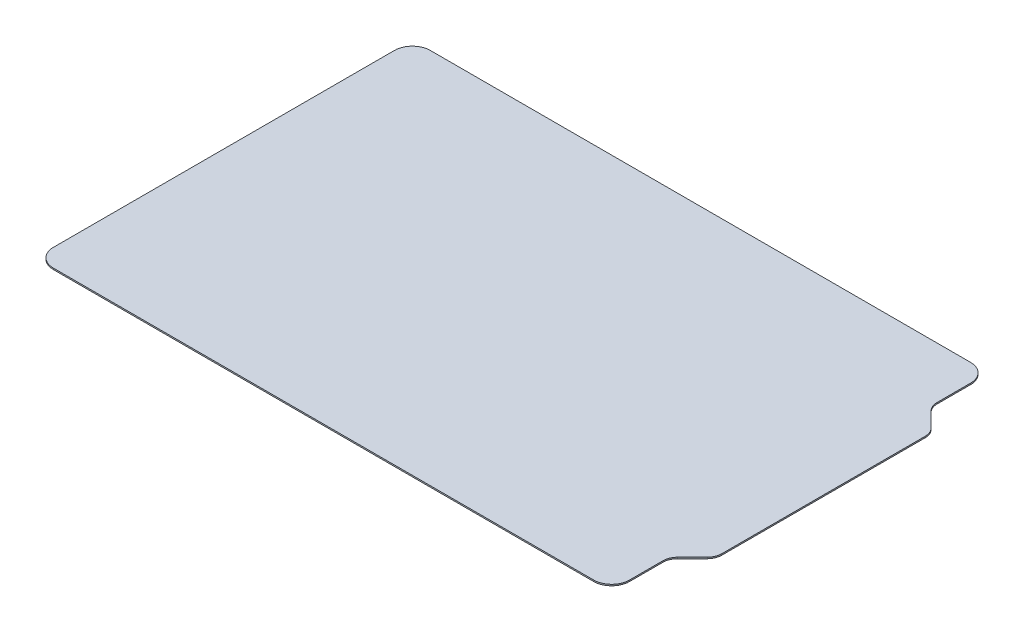
SolidWorks part; units mm, degrees
material "AISI 1020 Steel, Cold Rolled"
ref_plane "Front Plane" through (0, 0, 0) normal (0, 0, 1) x (1, 0, 0)
ref_plane "Top Plane" through (0, 0, 0) normal (0, 1, 0) x (1, 0, 0)
ref_plane "Right Plane" through (0, 0, 0) normal (1, 0, 0) x (0, 0, -1)
sketch "Sketch1" plane through (0, 0, 0) normal (0, 1, 0) x (1, 0, 0)
  line L1 (-167, 105) -> (167, 105)
  line L2 (-167, 105) -> (-167, -105)
  line L3 (-167, -105) -> (167, -105)
  line L4 (167, 105) -> (167, -105)
  line L5 (-167, 105) -> (167, -105) construction
  line L6 (-167, -105) -> (167, 105) construction
  point P0 (0, 0)
  dimension "D1" = 334
  dimension "D2" = 210
extrude "Boss-Extrude1" add sketch "Sketch1" along normal blind 0.76
sketch "Sketch2" plane through (0, 0, 0) normal (0, -1, 0) x (-1, 0, 0)
  line L0 (-167, -60) -> (-154, -73)
  line L5 (-167, -105) -> (-167, 105) construction
  line L6 (-154, -73) -> (-154, -105)
  line L7 (167, -105) -> (-167, -105) construction
  line L8 (-154, -105) -> (-167, -105)
  line L9 (-167, -105) -> (-167, -60)
  line L10 (-0.418, 0) -> (0.418, 0) construction
  line L11 (-154, 105) -> (-167, 105)
  line L12 (-154, 73) -> (-154, 105)
  line L13 (-167, 60) -> (-154, 73)
  line L14 (-167, 105) -> (-167, 60)
  dimension "D1" = 13
  dimension "D2" = 45
  dimension "D3" = 32
extrude "Cut-Extrude1" cut sketch "Sketch2" against normal blind 0.76
fillet "Fillet1" radius 8 4 edges at (154, 0.38, -73) (167, 0.38, -60) (154, 0.38, 73) (167, 0.38, 60)
fillet "Fillet2" radius 10 4 edges at (154, 0.38, -105) (-167, 0.38, -105) (-167, 0.38, 105) (154, 0.38, 105)
